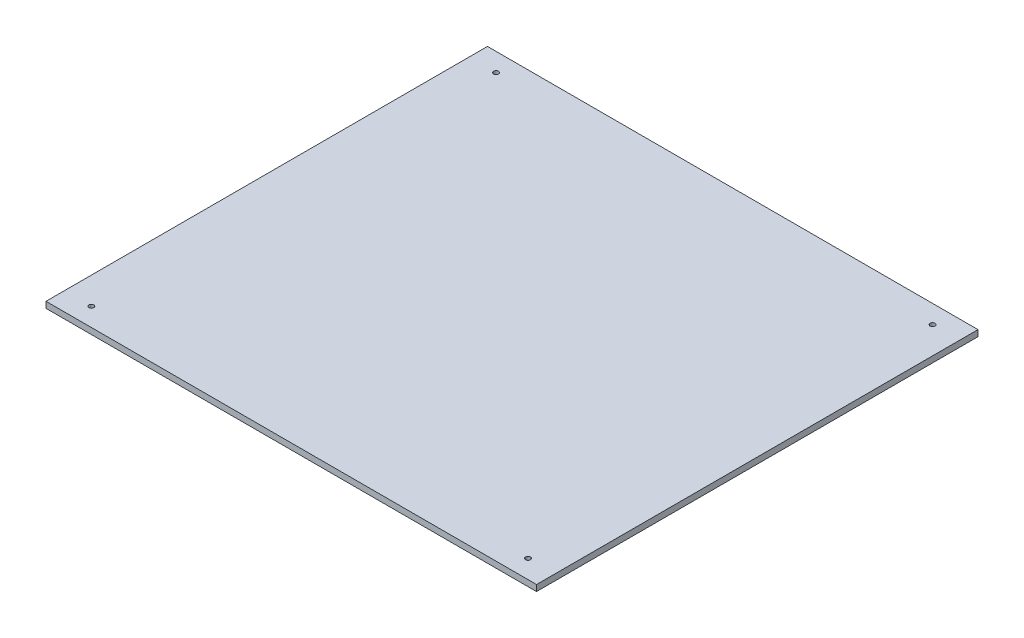
SolidWorks part; units mm, degrees
ref_plane "Front Plane" through (0, 0, 0) normal (0, 0, 1) x (1, 0, 0)
ref_plane "Top Plane" through (0, 0, 0) normal (0, 1, 0) x (1, 0, 0)
ref_plane "Right Plane" through (0, 0, 0) normal (1, 0, 0) x (0, 0, -1)
sketch "Sketch2" plane through (0, 0, 0) normal (0, 1, 0) x (1, 0, 0)
  line L1 (0, 0) -> (400, 0)
  line L2 (0, 0) -> (0, 360)
  line L3 (0, 360) -> (400, 360)
  line L4 (400, 0) -> (400, 360)
  dimension "D1" = 400
  dimension "D2" = 360
extrude "Boss-Extrude1" add sketch "Sketch2" along normal blind 5
sketch "Sketch3" plane through (0, 5, 0) normal (0, 1, 0) x (1, 0, 0)
  circle A0 centre (22, 15) radius 2
  point P2 (0, 0)
extrude "Cut-Extrude1" cut sketch "Sketch3" against normal through all
pattern_linear "LPattern1" count 2 spacing 330 along (0, 0, -1) count 2 spacing 356 along (1, 0, 0) of "Cut-Extrude1"
